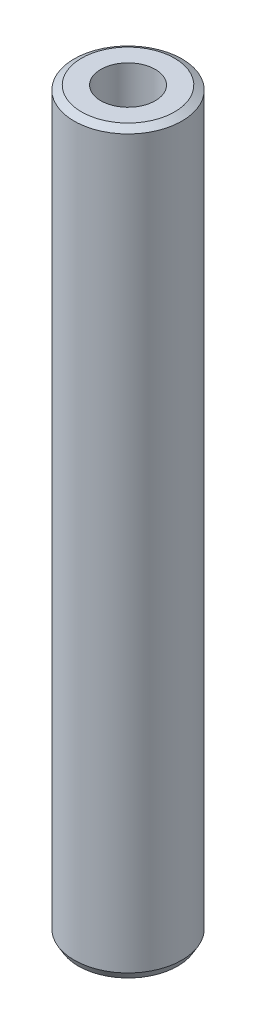
SolidWorks part; units mm, degrees
ref_plane "Front Plane" through (0, 0, 0) normal (0, 0, 1) x (1, 0, 0)
ref_plane "Top Plane" through (0, 0, 0) normal (0, 1, 0) x (1, 0, 0)
ref_plane "Right Plane" through (0, 0, 0) normal (1, 0, 0) x (0, 0, -1)
sketch "Sketch1" plane through (0, 0, 0) normal (0, 1, 0) x (1, 0, 0)
  circle A0 centre (0, 0) radius 22.5
  dimension "SHAFT_OD" = 45
extrude "Boss-Extrude1" add sketch "Sketch1" along normal blind 308.1064
sketch "Sketch2" plane through (0, 0, 0) normal (0, 1, 0) x (1, 0, 0)
  circle A0 centre (0, 0) radius 11.3654
  dimension "BORE_D" = 22.7308
extrude "Cut-Extrude1" cut sketch "Sketch2" along normal through all
chamfer "Chamfer1" distance 1.7761 angle 60 2 edges at (0, 308.1064, 22.5) (0, 0, 22.5) first distance on face at (0, 308.1064, 22.5) first distance on face at (0, 0, 11.3654)
